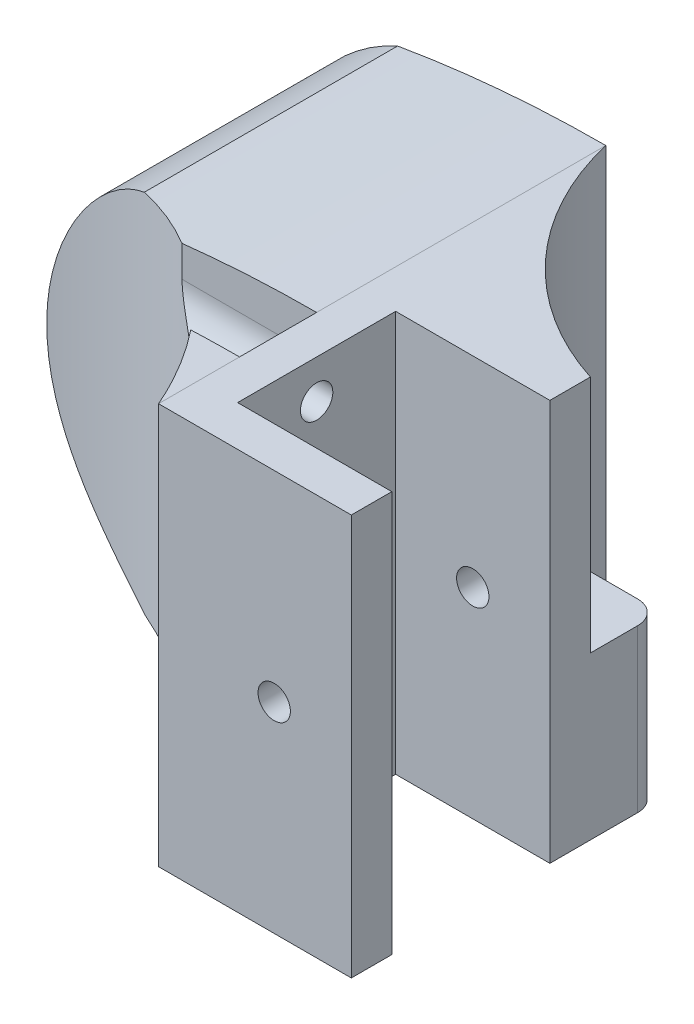
SolidWorks part; units mm, degrees
material "PBT Общее назначение"
ref_plane "Спереди" through (0, 0, 0) normal (0, 0, 1) x (1, 0, 0)
ref_plane "Сверху" through (0, 0, 0) normal (0, 1, 0) x (1, 0, 0)
ref_plane "Справа" through (0, 0, 0) normal (1, 0, 0) x (0, 0, -1)
sketch "Эскиз1" plane through (0, 0, 0) normal (0, 0, 1) x (1, 0, 0)
  line L0 (0, 0) -> (61.556, 0) construction
  line L1 (0, 26) -> (0, -26)
  line L2 (0, 26) -> (52, 26)
  line L3 (0, -26) -> (52, -26)
  line L4 (52, 26) -> (52, -26)
  line L5 (0, 0) -> (52, 0) construction
  dimension "D1" = 52
  dimension "D2" = 52
extrude "Бобышка-Вытянуть1" add sketch "Эскиз1" along normal blind 31
sketch "Эскиз2" plane through (0, 0, 0) normal (-1, 0, 0) x (0, 0, 1)
  line L0 (15.5, 26) -> (15.5, -26) construction
  line L1 (31, 26) -> (0, 26) construction
  line L2 (31, -26) -> (0, -26) construction
  line L3 (5.25, 26) -> (25.75, 26)
  line L4 (5.25, 26) -> (5.25, -26)
  line L5 (25.75, 26) -> (25.75, -26)
  line L6 (5.25, -26) -> (25.75, -26)
  line L7 (15.5, 26) -> (15.5, -26) construction
  dimension "D1" = 20.5
extrude "Вырез-Вытянуть1" cut sketch "Эскиз2" against normal blind 20
sketch "Эскиз3" plane through (52, 0, 0) normal (1, 0, 0) x (0, 0, -1)
  line L0 (-15.5, 26) -> (-15.5, -26) construction
  line L1 (-31, 26) -> (0, 26) construction
  line L2 (-31, -26) -> (0, -26) construction
  line L3 (-31, 0) -> (0, 0) construction
  line L4 (-31, -26) -> (-31, 26) construction
  line L5 (0, -26) -> (0, 26) construction
ref_plane "СимZ" through (0, 0, 15.5) normal (0, 0, 1) x (0, -1, 0)
ref_plane "СимY" through (0, 0, 0) normal (0, -1, 0) x (0, 0, -1)
sketch "Эскиз4" plane through (0, 26, 0) normal (0, 1, 0) x (1, 0, 0)
  line L0 (41.25, 0) -> (41.25, -31) construction
  line L1 (52, 0) -> (0, 0) construction
  line L2 (52, -31) -> (0, -31) construction
  line L3 (20, -25.75) -> (20, -5.25) construction
  line L4 (20, -25.75) -> (20, -5.25) construction
  dimension "D1" = 21.25
ref_plane "Симм Лента" through (41.25, 0, 0) normal (-1, 0, 0) x (0, 0, 1)
sketch "Эскиз5" plane through (0, 0, 31) normal (0, 0, 1) x (1, 0, 0)
  line L0 (41.25, 26) -> (41.25, -26) construction
  line L1 (0, -26) -> (52, -26) construction
  line L2 (52, 26) -> (0, 26) construction
  circle A0 centre (41.25, 0) radius 26
extrude "Бобышка-Вытянуть2" add sketch "Эскиз5" against normal up to surface (31 mm away) up to face at (26, 0, 0)
sketch "Эскиз6" plane through (0, 0, 31) normal (0, 0, 1) x (1, 0, 0)
  line L2 (52, 23.6736) -> (52, 26) construction
  line L3 (52, 26) -> (0, 26) construction
  line L4 (52, 23.6736) -> (52, 26)
  line L5 (52, 26) -> (25, 26)
  arc A0 (52, 23.6736) -> (25, 26) centre (25, -131.8405) ccw
  dimension "D1" = 25
extrude "Вырез-Вытянуть2" cut sketch "Эскиз6" against normal through all
mirror "Зеркальное отражение1" about plane through (0, 0, 0) normal (0, -1, 0) of "Вырез-Вытянуть2"
sketch "Эскиз7" plane through (0, 26, 0) normal (0, 1, 0) x (1, 0, 0)
  line L0 (20, -25.75) -> (20, -5.25) construction
  line L1 (20, -25.75) -> (0, -25.75) construction
  line L2 (20, -5.25) -> (0, -5.25) construction
  line L3 (20, -25.75) -> (20, -5.25)
  line L4 (20, -25.75) -> (0, -25.75)
  line L5 (20, -5.25) -> (0, -5.25)
  line L6 (0, -5.25) -> (0, -25.75)
extrude "Вырез-Вытянуть3" cut sketch "Эскиз7" against normal through all
sketch "Эскиз8" plane through (0, 26, 0) normal (0, 1, 0) x (1, 0, 0)
  line L0 (35.2, 15.75) -> (47.3, 15.75) construction
  line L1 (35.2, 15.75) -> (47.3, 15.75) construction
  line L2 (47.3, 8.35) -> (35.2, 8.35) construction
  line L3 (47.3, 8.35) -> (35.2, 8.35) construction
  line L4 (25, 0) -> (0, 0) construction
  dimension "D1" = 8.35
  dimension "D2" = 15.75
sketch "Эскиз9" plane through (0, 0, 0) normal (0, 0, -1) x (-1, 0, 0)
  line L0 (-25, 26) -> (-25, -26)
  arc A0 (-25, 26) -> (-52, 23.6736) centre (-25, -131.8405) ccw construction
  arc A1 (-52, 23.6736) -> (-52, -23.6736) centre (-41.25, 0) ccw construction
  arc A2 (-52, -23.6736) -> (-25, -26) centre (-25, 131.8405) ccw construction
  arc A3 (-25, 26) -> (-52, 23.6736) centre (-25, -131.8405) ccw
  arc A4 (-52, 23.6736) -> (-52, -23.6736) centre (-41.25, 0) ccw
  arc A5 (-52, -23.6736) -> (-25, -26) centre (-25, 131.8405) ccw
extrude "Бобышка-Вытянуть3" add sketch "Эскиз9" along normal blind 27
sketch "Эскиз10" plane through (41.25, 0, 0) normal (-1, 0, 0) x (0, 0, 1)
  line L0 (0, -26) -> (0, 26) construction
  line L1 (0, -26) -> (0, 26) construction
  line L2 (-6.75, 9) -> (-15.75, 9) construction
  line L3 (-6.75, 9) -> (-6.75, -9) construction
  line L4 (-15.75, 9) -> (-15.75, -9) construction
  line L5 (-6.75, -9) -> (-15.75, -9) construction
  line L6 (-15.75, 0) -> (-6.75, 0) construction
  line L7 (-27, -26) -> (-27, 26) construction
  line L8 (-27, -26) -> (-27, 26) construction
  line L9 (-27, 0) -> (0, 0) construction
  line L10 (-11.25, 9) -> (-11.25, -9) construction
  line L11 (-20.75, 14) -> (-1.75, 14)
  line L12 (-20.75, 14) -> (-20.75, 0)
  line L13 (-20.75, 0) -> (-1.75, 0)
  line L14 (-1.75, 0) -> (-1.75, 14)
  dimension "D1" = 15.75
  dimension "D2" = 9
  dimension "D3" = 18
  dimension "D4" = 5
  dimension "D5" = 5
  dimension "D6" = 5
revolve "Вырез-Повернуть2" cut sketch "Эскиз10" angle 360 about L13
sketch "Эскиз11" plane through (0, 0, 0) normal (0, -1, 0) x (0, 0, -1)
  line L0 (1.75, 27.25) -> (1.75, 55.25) construction
  line L1 (1.75, 27.25) -> (1.75, 55.25)
  line L2 (20.75, 55.25) -> (20.75, 27.25) construction
  line L3 (20.75, 55.25) -> (20.75, 27.25)
  line L4 (20.75, 55.25) -> (1.75, 55.25)
  line L5 (20.75, 27.25) -> (1.75, 27.25)
extrude "Вырез-Вытянуть4" cut sketch "Эскиз11" along normal through all
sketch "Эскиз12" plane through (0, -26, 0) normal (0, -1, 0) x (1, 0, 0)
  line L0 (0, 0) -> (25, 0) construction
  line L1 (25, -27) -> (25, 0) construction
  line L2 (0, 0) -> (25, 0)
  line L3 (25, -27) -> (25, 0)
  arc A0 (25, -27) -> (0, 0) centre (-11.4767, -35.7006) ccw
  dimension "D1" = 75
extrude "Бобышка-Вытянуть4" add sketch "Эскиз12" against normal up to surface (52 mm away) up to face at (11.25, 26, 15.5)
sketch "Эскиз13" plane through (0, 0, 31) normal (0, 0, 1) x (1, 0, 0)
  line L0 (10, -26) -> (10, 26) construction
  line L4 (20, 26) -> (0, 26)
  line L5 (20, -26) -> (20, 26)
  line L6 (0, -26) -> (20, -26)
  line L7 (0, 26) -> (0, -26)
  line L8 (20, 26) -> (0, 26) construction
  line L9 (20, -26) -> (20, 26) construction
  line L10 (0, -26) -> (20, -26) construction
  line L11 (0, 26) -> (0, -26) construction
  circle A0 centre (10, 0) radius 2.1
  dimension "D2" = 4.2
  dimension "D1" = 0
extrude "Вырез-Вытянуть5" cut sketch "Эскиз13" against normal through all
sketch "Эскиз14" plane through (20, 0, 0) normal (-1, 0, 0) x (0, 0, 1)
  line L0 (15.5, -26) -> (15.5, 26) construction
  line L4 (5.25, 26) -> (5.25, -26)
  line L5 (5.25, -26) -> (25.75, -26)
  line L6 (25.75, -26) -> (25.75, 26)
  line L7 (25.75, 26) -> (5.25, 26)
  line L8 (5.25, 26) -> (5.25, -26) construction
  line L9 (5.25, -26) -> (25.75, -26) construction
  line L10 (25.75, -26) -> (25.75, 26) construction
  line L11 (25.75, 26) -> (5.25, 26) construction
  circle A0 centre (15.5, -21) radius 2.1
  circle A1 centre (15.5, 21) radius 2.1
  dimension "D2" = 5
  dimension "D3" = 4.2
  dimension "D4" = 4.2
  dimension "D5" = 5
  dimension "D1" = 0
extrude "Вырез-Вытянуть6" cut sketch "Эскиз14" against normal through all
ref_plane "Плоскость1" through (25, 0, 0) normal (1, 0, 0) x (0, 0, -1)
sketch "Эскиз15" plane through (25, 0, 0) normal (1, 0, 0) x (0, 0, -1)
  circle A0 centre (-15.5, 21) radius 2.1 construction
  circle A1 centre (-15.5, 21) radius 2.1 construction
  circle A2 centre (-15.5, -21) radius 2.1 construction
  circle A3 centre (-15.5, -21) radius 2.1 construction
  circle A4 centre (-15.5, 21) radius 5
  circle A5 centre (-15.5, -21) radius 5
  dimension "D1" = 10
  dimension "D2" = 10
extrude "Вырез-Вытянуть7" cut sketch "Эскиз15" along normal through all
sketch "Эскиз16" plane through (20, 0, 0) normal (-1, 0, 0) x (0, 0, 1)
  line L0 (17.6, 21) -> (13.4, 21) construction
  circle A0 centre (15.5, 21) radius 2.1 construction
ref_plane "Плоскость2" through (0, 21, 0) normal (0, 1, 0) x (0, 0, -1)
sketch "Эскиз17" plane through (0, 21, 0) normal (0, 1, 0) x (0, 0, -1)
  line L0 (-20.5, -25) -> (-10.5, -25) construction
  line L1 (-20.5, -25) -> (-10.5, -25)
  line L2 (-10.5, -25) -> (-10.5, -67.25)
  line L3 (-20.5, -25) -> (-20.5, -67.25)
  line L5 (27, -67.25) -> (27, -52) construction
  line L6 (27, -67.25) -> (27, -52) construction
  line L7 (-10.5, -67.25) -> (-20.5, -67.25)
  line L8 (27, -67.25) -> (-10.5, -67.25) construction
extrude "Вырез-Вытянуть8" cut sketch "Эскиз17" along normal through all
mirror "Зеркальное отражение2" about plane through (0, 0, 0) normal (0, -1, 0) of "Вырез-Вытянуть8"
ref_plane "Плоскость3" through (0, 0, 0) normal (0, 0, -1) x (-1, 0, 0)
sketch "Эскиз18" plane through (0, 0, 0) normal (0, 0, -1) x (-1, 0, 0)
  circle A0 centre (-10, 0) radius 2.1 construction
  circle A1 centre (-10, 0) radius 2.1 construction
  circle A2 centre (-10, 0) radius 5
  dimension "D1" = 10
extrude "Вырез-Вытянуть9" cut sketch "Эскиз18" along normal through all
sketch "Эскиз19" plane through (0, 0, 31) normal (0, 0, 1) x (1, 0, 0)
  arc A0 (52, -23.6736) -> (52, 23.6736) centre (41.25, 0) ccw construction
  arc A1 (52, -23.6736) -> (52, 23.6736) centre (41.25, 0) ccw construction
  circle A2 centre (41.25, 0) radius 26 construction
  circle A3 centre (41.25, 0) radius 2.5
  dimension "D1" = 5
extrude "Вырез-Вытянуть10" cut sketch "Эскиз19" against normal through all
ref_plane "Зеркало" through (0, 0, 0) normal (-1, 0, 0) x (0, 0, 1)
mirror "Зеркальное отражение3" about plane through (0, 0, 0) normal (-1, 0, 0) of bodies 147
sketch "Sketch1" plane through (0, 26, 0) normal (0, 1, 0) x (1, 0, 0)
  line L0 (-27.25, 1.75) -> (-52, 1.75) construction
  line L1 (-27.25, 1.75) -> (-52, 1.75) construction
  line L2 (-52, 27) -> (-67.25, 27) construction
  line L3 (-67.25, -31) -> (-52, -31) construction
  line L4 (-52, 27) -> (-67.25, 27) construction
  line L5 (-67.25, -31) -> (-25, -31)
  line L6 (-27.25, -3.25) -> (-67.25, -3.25) construction
  line L7 (-67.25, -31) -> (-67.25, -3.25)
  line L8 (-67.25, -3.25) -> (-67.25, 27) construction
  arc A0 (-25, -31) -> (-67.25, -3.25) centre (-67.25, -49.2883) ccw
  point P11 (-67.25, -3.25)
  dimension "D1" = 5
extrude "Cut-Extrude1" cut sketch "Sketch1" against normal through all
sketch "Sketch2" plane through (0, 0, 0) normal (0, -1, 0) x (0, 0, -1)
  line L0 (27, -43.75) -> (27, -38.75) construction
  line L1 (27, -43.75) -> (27, -38.75) construction
  line L2 (27, -41.25) -> (-65.2716, -41.25) construction
  line L3 (-9.6995, -43.75) -> (-9.6995, 25.882) construction
  arc A0 (-9.6995, -43.75) -> (-13.132, -38.75) centre (-49.2883, -67.25) ccw construction
  arc A1 (-9.6995, -43.75) -> (-13.132, -38.75) centre (-49.2883, -67.25) ccw construction
ref_plane "Plane1" through (0, 0, 9.6995) normal (0, 0, 1) x (1, 0, 0)
sketch "Sketch3" plane through (0, 0, 9.6995) normal (0, 0, 1) x (1, 0, 0)
  circle A0 centre (-41.25, 0) radius 2.5 construction
  circle A1 centre (-41.25, 0) radius 2.5 construction
  circle A2 centre (-41.25, 0) radius 7.5
  dimension "D1" = 15
extrude "Cut-Extrude2" cut sketch "Sketch3" against normal blind 2 and the other way through all
delete or keep bodies "Body-Delete/Keep 1" type delete bodies bodies 147
sketch "Эскиз23" plane through (0, 0, 0) normal (0, 0, -1) x (-1, 0, 0)
  line L0 (10, 5) -> (0, 5)
  line L1 (0, 26) -> (0, -26) construction
  line L2 (0, 5) -> (0, -5)
  line L3 (10, -5) -> (0, -5)
  line L4 (15, 0) -> (15, -5)
  line L5 (15, -5) -> (10, -5)
  circle A0 centre (10, 0) radius 5 construction
  arc A1 (15, 0) -> (10, 5) centre (10, 0) ccw
extrude "Вырез-Вытянуть12" cut sketch "Эскиз23" along normal through all
sketch "Эскиз20" plane through (0, -26, 0) normal (0, -1, 0) x (1, 0, 0)
  line L0 (-4, 5.25) -> (-16, 5.25) construction
  line L1 (-4, 5.25) -> (-4, -2.75) construction
  line L2 (-16, 5.25) -> (-16, -2.75) construction
  line L3 (-4, -2.75) -> (-16, -2.75) construction
  line L4 (-20, 5.25) -> (0, 5.25) construction
  line L5 (0, 5.25) -> (0, 0) construction
  line L6 (0, 5.25) -> (-20, 5.25)
  line L7 (0, 5.25) -> (0, -9.14)
  line L8 (-20, 5.25) -> (-20, -9.14)
  line L9 (0, -9.14) -> (-20, -9.14)
  dimension "D1" = 4
  dimension "D2" = 12
  dimension "D3" = 8
  dimension "D4" = 14.39
extrude "Бобышка-Вытянуть5" add sketch "Эскиз20" against normal up to surface (21 mm away) up to face at (-10.181, -5, -2.7512)
sketch "Эскиз22" plane through (0, -26, 0) normal (0, -1, 0) x (1, 0, 0)
  line L0 (-4, -2.75) -> (-16, -2.75) construction
  line L1 (-16, 5.25) -> (-16, -2.75) construction
  line L2 (-4, 5.25) -> (-4, -2.75) construction
  line L3 (-4, -2.75) -> (-16, -2.75) construction
  line L4 (-16, 5.25) -> (-16, -2.75) construction
  line L5 (-4, 5.25) -> (-4, -2.75) construction
  line L6 (-10, -1.25) -> (-10, 1.9254) construction
  line L7 (-10, 1.9254) -> (-12.75, 0.3377)
  line L8 (-12.75, 0.3377) -> (-12.75, -2.8377)
  line L9 (-12.75, -2.8377) -> (-10, -4.4254)
  line L10 (-10, -4.4254) -> (-7.25, -2.8377)
  line L11 (-7.25, -2.8377) -> (-7.25, 0.3377)
  line L12 (-7.25, 0.3377) -> (-10, 1.9254)
  line L13 (-10, -2.75) -> (-10, -1.25) construction
  line L14 (0, 5.25) -> (0, -9.14) construction
  line L16 (-10, -1.25) -> (0, -1.25) construction
  line L17 (-20, 5.25) -> (0, 5.25) construction
  circle A0 centre (-10, -1.25) radius 2.75 construction
  dimension "D1" = 5.5
  dimension "D2" = 3
  dimension "D3" = 10
  dimension "D4" = 6.5
extrude "Вырез-Вытянуть11" cut sketch "Эскиз22" against normal blind 15
fillet "Скругление1" radius 3 1 edges at (0, -15.5, -9.14)
